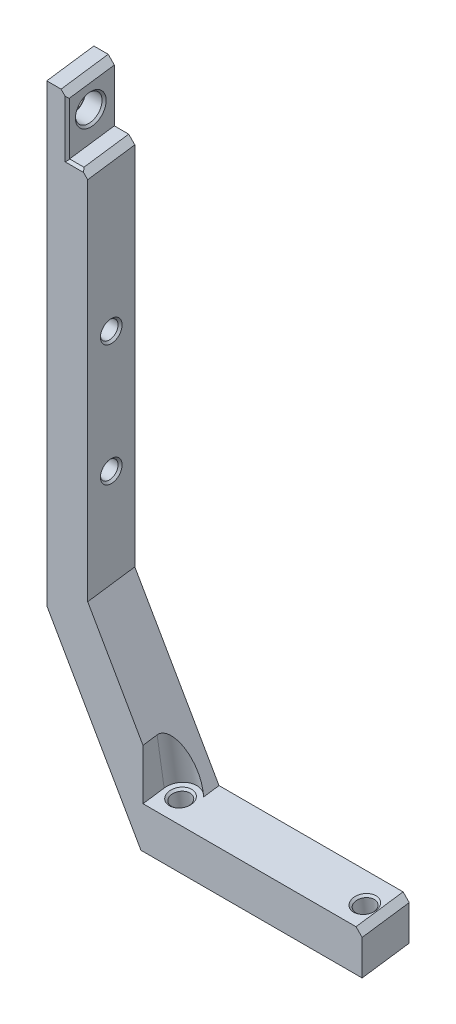
SolidWorks part; units mm, degrees
ref_plane "Top" through (0, 0, 0) normal (0, 0, 1) x (1, 0, 0)
ref_plane "Front" through (0, 0, 0) normal (0, 1, 0) x (1, 0, 0)
ref_plane "Right" through (0, 0, 0) normal (1, 0, 0) x (0, 0, -1)
sketch "Sketch4" plane through (0, 0, 0) normal (1, 0, 0) x (0, 0, -1)
  line L1 (0, 0) -> (11.5, 0)
  line L2 (0, 0) -> (0, 144)
  line L3 (0, 144) -> (11.5, 144)
  line L4 (11.5, 0) -> (11.5, 144)
  dimension "D1" = 11.5
  dimension "D2" = 144
extrude "Boss-Extrude2" add sketch "Sketch4" along normal blind 10
sketch "Sketch6" plane through (10, 0, 0) normal (1, 0, 0) x (0, 0, -1)
  line L0 (5.75, 0) -> (11.5, 0.8081)
  line L1 (0, 0) -> (11.5, 0) construction
  line L2 (11.5, 0) -> (11.5, 144) construction
  line L3 (11.5, 0.8081) -> (10.1083, 10.7108)
  line L4 (10.1083, 10.7108) -> (0.2056, 9.3191)
  line L5 (0.2056, 9.3191) -> (1.5973, -0.5836)
  line L6 (1.5973, -0.5836) -> (5.75, 0)
  line L7 (0, 144) -> (0, 0) construction
  dimension "D1" = 10
  dimension "D2" = 10
  dimension "D3" = 82
extrude "Boss-Extrude3" add sketch "Sketch6" along normal blind 67 and the other way blind 10
sketch "Sketch26" plane through (0, 1.6006, -11.3886) normal (0, 0.1392, -0.9903) x (-1, 0, 0)
  line L0 (-23, -0.8002) -> (0, 39.0369)
  line L1 (-10, -0.8002) -> (-77, -0.8002) construction
  line L2 (0, -1.6005) -> (0, 140.9981) construction
  line L3 (0, 39.0369) -> (-10, 44.8104)
  line L4 (-10, -0.8002) -> (-10, 140.9981) construction
  line L5 (-10, 44.8104) -> (-33, 4.9733)
  line L7 (-23, -0.8002) -> (-33, 4.9733)
  dimension "D1" = 23
  dimension "D2" = 60
extrude "Boss-Extrude6" add sketch "Sketch26" along normal up to surface and the other way up to surface up to face at (6, 57.7616, -11.5) other way up to face at (5, 72, 0)
sketch "Sketch7" plane through (10, 0, 0) normal (1, 0, 0) x (0, 0, -1)
  line L0 (-3.1126, -1.2456) -> (11.8209, -3.029)
  line L2 (11.8209, -3.029) -> (11.8209, 0.8532)
  line L3 (11.8209, 0.8532) -> (-3.1126, -1.2456)
  line L4 (1.5973, -0.5836) -> (11.5, 0.8081) construction
extrude "Cut-Extrude2" cut sketch "Sketch7" against normal blind 10
sketch "Sketch8" plane through (0, 9.1102, 1.2804) normal (0, 0.9903, 0.1392) x (1, 0, 0)
  line L0 (30.5598, 1.5005) -> (77, 1.5005) construction
  line L1 (77, 11.5005) -> (77, 1.5005) construction
  circle A0 centre (72.5, 6.5005) radius 2.25
  circle A1 centre (27.5, 6.5005) radius 2.25
  dimension "D2" = 4.5
  dimension "D3" = 4.5
  dimension "D1" = 45
  dimension "D4" = 5
  dimension "D5" = 4.5
extrude "Cut-Extrude3" cut sketch "Sketch8" against normal through all
sketch "Sketch11" plane through (0, 9.1102, 1.2804) normal (0, 0.9903, 0.1392) x (1, 0, 0)
  line L0 (23.5, 6.5005) -> (23.5, 0)
  line L1 (23.5, 0) -> (31.5, 0)
  line L3 (31.5, 0) -> (31.5, 6.5005)
  line L4 (10, 0) -> (0, 0) construction
  circle A0 centre (27.5, 6.5005) radius 4 construction
  arc A1 (31.5, 6.5005) -> (23.5, 6.5005) centre (27.5, 6.5005) ccw
  dimension "D1" = 8
sketch "Sketch12" plane through (77, 0, 0) normal (1, 0, 0) x (0, 0, -1)
  line L5 (0.2056, 9.3191) -> (10.1083, 10.7108) construction
  line L13 (1.5973, -0.5836) -> (0, -0.8081)
  line L14 (0, -0.8081) -> (0, 9.2902)
  line L16 (1.5973, -0.5836) -> (11.5, 0.8081) construction
  line L17 (0, 21.9298) -> (0, 0) construction
  line L18 (11.5, 0.8081) -> (11.5, 10.9064)
  line L20 (11.5, 10.9064) -> (10.1083, 10.7108)
  line L21 (10.1083, 10.7108) -> (11.5, 0.8081)
  line L22 (10.1083, 10.7108) -> (0.2056, 9.3191) construction
  line L23 (11.5, 0.8081) -> (11.5, 23.5461) construction
  line L25 (11.5, 0.8081) -> (10.1083, 10.7108) construction
  line L26 (0, 9.2902) -> (0.2056, 9.3191)
  line L27 (0.2056, 9.3191) -> (1.5973, -0.5836)
  line L28 (0.2056, 9.3191) -> (1.5973, -0.5836) construction
extrude "Boss-Extrude4" add sketch "Sketch12" against normal up to surface (77 mm away) up to face at (0, 48.0374, -4.3521)
sketch "Sketch13" plane through (10, 0, 0) normal (1, 0, 0) x (0, 0, -1)
  line L0 (11.5, 144) -> (11.5, 152)
  line L1 (11.5, 152) -> (0, 150.3838)
  line L2 (0, 150.3838) -> (0, 144)
  line L3 (0, 144) -> (11.5, 144)
  line L4 (11.5, 10.9064) -> (0, 9.2902) construction
  dimension "D1" = 8
extrude "Boss-Extrude5" add sketch "Sketch13" against normal blind 10
sketch "Sketch14" plane through (10, 0, 0) normal (1, 0, 0) x (0, 0, -1)
  line L0 (11.5, 10.9064) -> (11.5, 23.5461) construction
  circle A0 centre (5.75, 144) radius 3.25
  dimension "D2" = 6.5
  dimension "D1" = 8
  dimension "D3" = 5.75
extrude "Cut-Extrude5" cut sketch "Sketch14" against normal blind 10
sketch "Sketch18" plane through (10, 0, 0) normal (1, 0, 0) x (0, 0, -1)
  line L0 (5.75, 99.6) -> (5.75, 70)
  line L1 (11.5, 10.9064) -> (11.5, 23.5461) construction
  dimension "D1" = 5.75
  dimension "D2" = 29.6
  dimension "D3" = 70
hole_wizard "M4 Clearance Hole1" positions "Sketch19" profile "Sketch20" hole size "M4" standard "DIN" end condition through all
sketch "Sketch19" plane through (10, 0, 0) normal (1, 0, 0) x (0, 0, -1)
  point P0 (5.75, 70)
  point P3 (5.75, 99.6)
sketch "Sketch20" plane through (10, 70, -5.75) normal (0, 1, 0) x (0, 0, -1)
  line L0 (0, 0) -> (0, 10)
  line L1 (0, 10) -> (2.15, 10)
  line L2 (2.15, 10) -> (2.15, 0)
  line L5 (2.15, 0) -> (0, 0)
  line L11 (0, -6.35) -> (0, 107.95) construction
  dimension "Thru Hole Dia." = 4.3
  dimension "Thru Hole Depth" = 10
sketch "Sketch24" plane through (10, 0, 0) normal (1, 0, 0) x (0, 0, -1)
  line L0 (11.5, 152) -> (0, 150.3838)
  line L1 (0, 150.3838) -> (0, 136)
  line L2 (0, 150.3838) -> (0, 45.2508) construction
  line L3 (0, 136) -> (11.5, 137.6162)
  line L4 (11.5, 10.9064) -> (11.5, 23.5461) construction
  line L5 (11.5, 137.6162) -> (11.5, 152)
  circle A0 centre (5.75, 144) radius 3.25 construction
  dimension "D1" = 8
extrude "Cut-Extrude7" cut sketch "Sketch24" against normal blind 5
chamfer "Chamfer2" distance 0.5 angle 45 10 edges at (10, 70, -7.9) (0, 70, -7.9) (10, 99.6, -7.9) (0, 99.6, -7.9) (0, 144, -9) (27.5, 0.4254, -8.7768) (72.5, 9.7018, -2.9288) (72.5, 0.4254, -8.7768) (5, 144, -9) (27.5, 9.7018, -2.9288)
chamfer "Chamfer5" distance 0.5 angle 45 2 edges at (7.5, 136, 0) (5, 143.1919, 0) first distance on face at (12.4088, 13.5034, 0)
chamfer "Chamfer6" distance 1.5 angle 45 2 edges at (5, 151.227, -6) (10, 136.849, -6.0409)
chamfer "Chamfer7" distance 1.5 angle 45 1 edges at (77, 10.0983, -5.75)
sketch "Sketch28" plane through (0, 1.6006, -11.3886) normal (0, 0.1392, -0.9903) x (-1, 0, 0)
  line L0 (-31.0986, -14.8274) -> (8.299, -43.6267)
  line L1 (8.299, -43.6267) -> (8.299, 53.4112)
  line L2 (8.299, 53.4112) -> (-31.0986, -14.8274)
  line L3 (-10, 21.7164) -> (-17.2265, 9.1998) construction
  point P6 (0, 0)
  point P7 (-31.0986, -14.8274)
extrude "Cut-Extrude8" cut sketch "Sketch28" against normal through all and the other way through all
ref_plane "Plane1" through (87, 0, 0) normal (1, 0, 0) x (0, 0, -1)
extrude "Cut-Extrude9" cut sketch "Sketch11" along normal through all
sketch "Sketch29" plane through (0, -0.7925, -0.1114) normal (0, -0.9903, -0.1392) x (1, 0, 0)
  circle A0 centre (27.5, -6.5005) radius 2.25
  dimension "D1" = 4.5
extrude "Cut-Extrude10" cut sketch "Sketch29" against normal through all
chamfer "Chamfer10" distance 0.5 angle 45 1 edges at (27.5, 9.7018, -2.9288)
